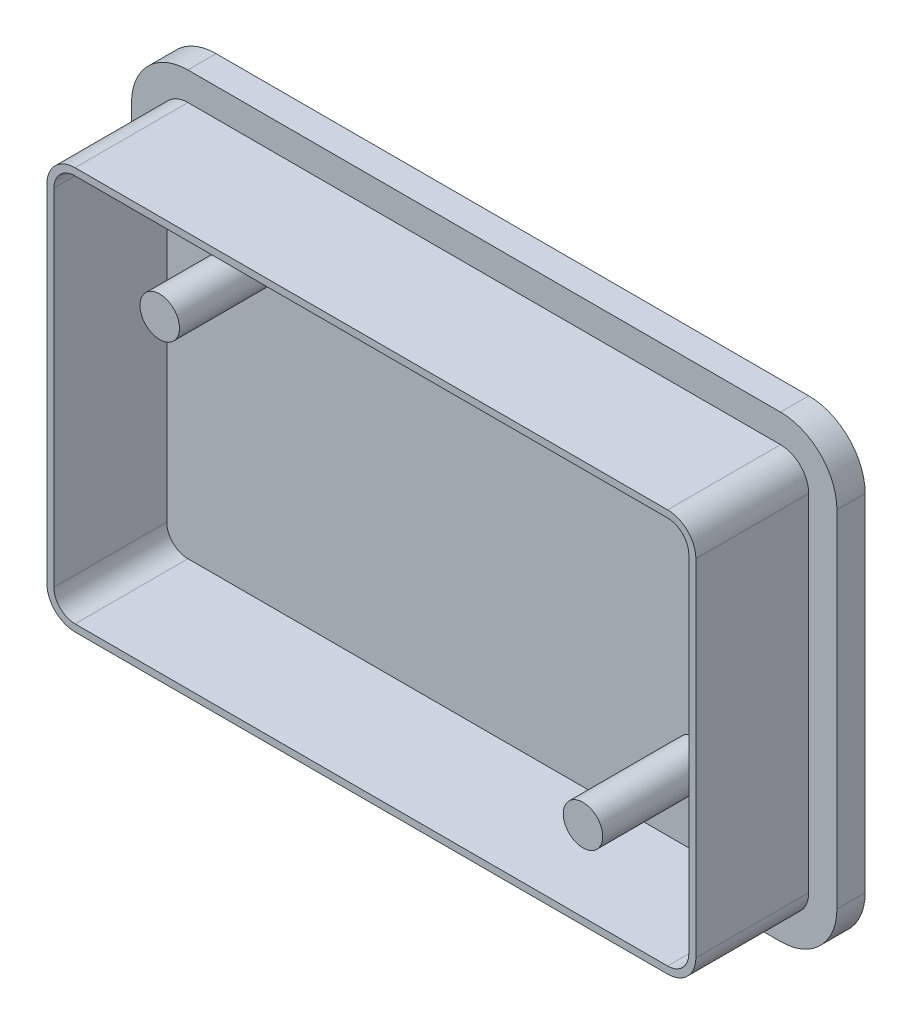
SolidWorks part; units mm, degrees
ref_plane "Front Plane" through (0, 0, 0) normal (0, 0, 1) x (1, 0, 0)
ref_plane "Top Plane" through (0, 0, 0) normal (0, 1, 0) x (1, 0, 0)
ref_plane "Right Plane" through (0, 0, 0) normal (1, 0, 0) x (0, 0, -1)
sketch "Sketch1" plane through (0, 0, 0) normal (0, 0, 1) x (1, 0, 0)
  line L0 (-21, 14.25) -> (21, 14.25)
  line L1 (-21, -16.25) -> (21, -16.25)
  line L2 (-25, -12.25) -> (-25, 12.25)
  line L3 (-21, 16.25) -> (21, 16.25)
  line L4 (25, -12.25) -> (25, 12.25)
  line L5 (-25, -16.25) -> (25, 16.25) construction
  line L6 (-25, 16.25) -> (25, -16.25) construction
  line L7 (23, -12.25) -> (23, 12.25)
  line L8 (-21, -14.25) -> (21, -14.25)
  line L9 (-23, -12.25) -> (-23, 12.25)
  line L10 (-21, 13.75) -> (21, 13.75)
  line L11 (22.5, -12.25) -> (22.5, 12.25)
  line L12 (-21, -13.75) -> (21, -13.75)
  line L13 (-22.5, -12.25) -> (-22.5, 12.25)
  arc A0 (21, 16.25) -> (25, 12.25) centre (21, 12.25) cw
  arc A1 (21, -16.25) -> (25, -12.25) centre (21, -12.25) ccw
  arc A2 (-21, -16.25) -> (-25, -12.25) centre (-21, -12.25) cw
  arc A3 (-25, 12.25) -> (-21, 16.25) centre (-21, 12.25) cw
  arc A4 (21, 14.25) -> (23, 12.25) centre (21, 12.25) cw
  arc A5 (21, -14.25) -> (23, -12.25) centre (21, -12.25) ccw
  arc A6 (-21, -14.25) -> (-23, -12.25) centre (-21, -12.25) cw
  arc A7 (-23, 12.25) -> (-21, 14.25) centre (-21, 12.25) cw
  arc A8 (21, 13.75) -> (22.5, 12.25) centre (21, 12.25) cw
  arc A9 (21, -13.75) -> (22.5, -12.25) centre (21, -12.25) ccw
  arc A10 (-21, -13.75) -> (-22.5, -12.25) centre (-21, -12.25) cw
  arc A11 (-22.5, 12.25) -> (-21, 13.75) centre (-21, 12.25) cw
  circle A12 centre (-15, 8.1) radius 1.4
  circle A13 centre (15, -8.1) radius 1.4
  point P0 (0, 0)
  point P50 (25, 0)
  dimension "D2" = 4
  dimension "D6" = 2.8
  dimension "D7" = 2.8
  dimension "D1" = 50
  dimension "D3" = 32.5
  dimension "D8" = 30
  dimension "D9" = 16.2
  dimension "D10" = 15
  dimension "D11" = 8.1
  dimension "D4" = 2
  dimension "D5" = 0.5
extrude "Boss-Extrude1" add sketch "Sketch1" along normal blind 2 contours A3 L2 A2 L1 A1 L4 A0 L3 L9 A7 L0 A4 L7 A5 L8 A6 | A11 L13 A10 L12 A9 L11 A8 L10 A13 A12 | A12 | A13 | A7 L9 A6 L8 A5 L7 A4 L0 L13 A11 L10 A8 L11 A9 L12 A10 region at (0, 14.1959, 0) region at (-23.4067, -14.6567, 0) region at (0, 0, 0) region at (-15, 8.1, 0) region at (15, -8.1, 0)
extrude "Boss-Extrude2" add sketch "Sketch1<3>" along normal blind 10 contours A12 | A13 | A7 L9 A6 L8 A5 L7 A4 L0 L13 A11 L10 A8 L11 A9 L12 A10 region at (0, 14.1959, 0) region at (-15, 8.1, 0) region at (15, -8.1, 0)
sketch "Sketch1<3>" plane through (0, 0, 0) normal (0, 0, 1) x (1, 0, 0) same geometry as "Sketch1"
